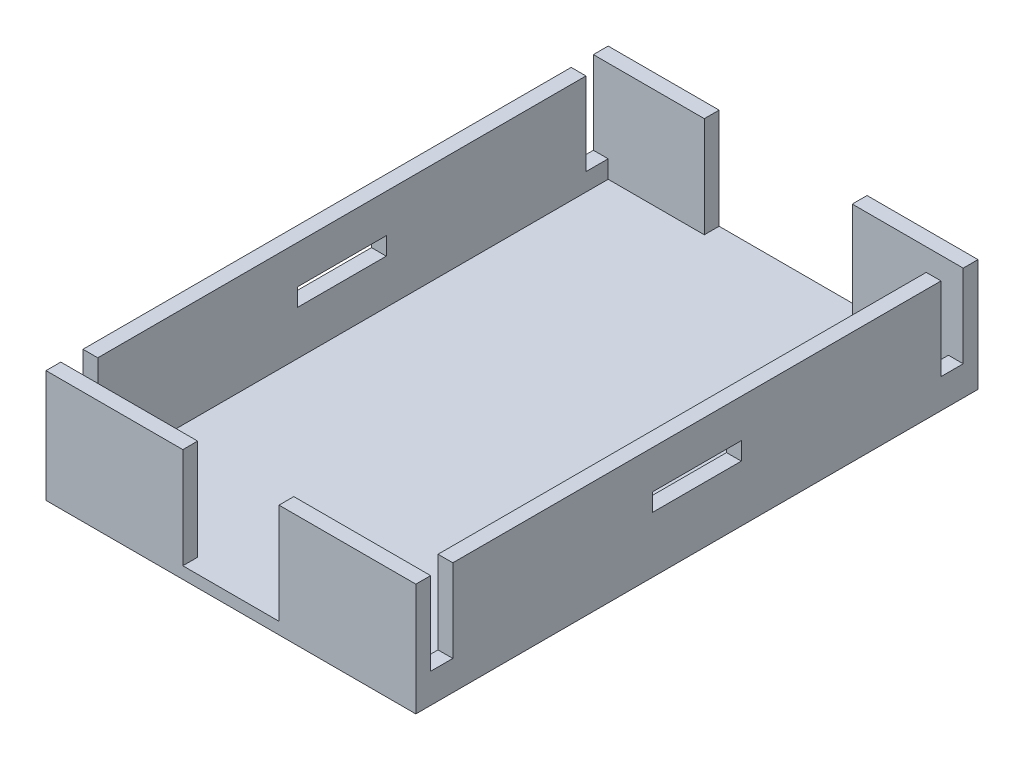
SolidWorks part; units mm, degrees
ref_plane "Front Plane" through (0, 0, 0) normal (0, 0, 1) x (1, 0, 0)
ref_plane "Top Plane" through (0, 0, 0) normal (0, 1, 0) x (1, 0, 0)
ref_plane "Right Plane" through (0, 0, 0) normal (1, 0, 0) x (0, 0, -1)
sketch "Sketch1" plane through (0, 0, 0) normal (0, 1, 0) x (1, 0, 0)
  line L1 (-12.5, -19) -> (12.5, -19)
  line L2 (-12.5, -19) -> (-12.5, 19)
  line L3 (-12.5, 19) -> (12.5, 19)
  line L4 (12.5, -19) -> (12.5, 19)
  line L5 (-12.5, -19) -> (12.5, 19) construction
  line L6 (-12.5, 19) -> (12.5, -19) construction
  point P0 (0, 0)
  dimension "D1" = 25
  dimension "D2" = 38
extrude "Boss-Extrude1" add sketch "Sketch1" along normal blind 7.6
sketch "Sketch2" plane through (0, 7.6, 0) normal (0, 1, 0) x (1, 0, 0)
  line L0 (-12.5, 19) -> (-12.5, -19) construction
  line L1 (-11.5, -18) -> (11.5, -18)
  line L2 (-11.5, -18) -> (-11.5, 18)
  line L3 (-11.5, 18) -> (11.5, 18)
  line L4 (11.5, -18) -> (11.5, 18)
  line L5 (-11.5, -18) -> (11.5, 18) construction
  line L6 (-11.5, 18) -> (11.5, -18) construction
  line L7 (-11.5, 18) -> (-12.5, 18)
  line L8 (-11.5, 18) -> (-11.5, 16.5)
  line L9 (-11.5, 16.5) -> (-12.5, 16.5)
  line L10 (-12.5, 18) -> (-12.5, 16.5)
  line L11 (0, -55) -> (0, 55) construction
  line L12 (11.5, 16.5) -> (12.5, 16.5)
  line L13 (12.5, 18) -> (12.5, 16.5)
  line L14 (11.5, 18) -> (12.5, 18)
  line L15 (-55, 0) -> (55, 0) construction
  line L16 (11.5, -16.5) -> (12.5, -16.5)
  line L17 (12.5, -18) -> (12.5, -16.5)
  line L18 (11.5, -18) -> (12.5, -18)
  line L19 (-11.5, -16.5) -> (-12.5, -16.5)
  line L20 (-12.5, -18) -> (-12.5, -16.5)
  line L21 (-11.5, -18) -> (-12.5, -18)
  point P0 (0, 0)
  line M5 (12.5, -19) -> (12.5, 19)
  line M7 (-12.5, 19) -> (-12.5, -19)
  dimension "D1" = 23
  dimension "D2" = 36
  dimension "D3" = 1.5
extrude "Cut-Extrude1" cut sketch "Sketch2" against normal blind 6.8 contours L1 L4 L3 L2 region at (0, 7.6, 0)
extrude "Cut-Extrude2" cut sketch "Sketch2<3>" against normal blind 5.6 contours L9 L2 L7 M7 | L14 L4 L12 M5 | L21 L2 L19 M7 | L4 L18 L16 M5 region at (-12, 7.6, 17.25) region at (12, 7.6, 17.25) region at (-12, 7.6, -17.25) region at (12, 7.6, -17.25)
sketch "Sketch2<3>" plane through (0, 7.6, 0) normal (0, 1, 0) x (1, 0, 0) same geometry as "Sketch2"
sketch "Sketch3" plane through (0, 0, 0) normal (1, 0, 0) x (0, 0, -1)
  line L0 (0, 0) -> (0, 7.6) construction
  line L1 (-16.5, 7.6) -> (16.5, 7.6) construction
  line L2 (-19, 0) -> (19, 0) construction
  line L3 (-3, 3.8) -> (3, 3.8)
  line L4 (-3, 3.8) -> (-3, 5)
  line L5 (-3, 5) -> (3, 5)
  line L6 (3, 3.8) -> (3, 5)
  line L7 (-3, 3.8) -> (3, 5) construction
  line L8 (-3, 5) -> (3, 3.8) construction
  point P5 (0, 4.4)
  dimension "D1" = 6
  dimension "D2" = 1.2
  dimension "D3" = 3.8
extrude "Cut-Extrude3" cut sketch "Sketch3" against normal through all both and the other way through all
sketch "Sketch4" plane through (0, 7.6, 0) normal (0, 1, 0) x (1, 0, 0)
  line L0 (0, -18) -> (0, -19) construction
  line L1 (-12.5, -18) -> (12.5, -18) construction
  line L2 (-12.5, -19) -> (12.5, -19) construction
  line L3 (0, 18) -> (0, 19) construction
  line L4 (-3.25, -19) -> (3.25, -19)
  line L5 (-3.25, -19) -> (-3.25, -18)
  line L6 (-3.25, -18) -> (3.25, -18)
  line L7 (3.25, -19) -> (3.25, -18)
  line L8 (-3.25, -19) -> (3.25, -18) construction
  line L9 (-3.25, -18) -> (3.25, -19) construction
  line L10 (-12.5, 18) -> (12.5, 18) construction
  line L11 (12.5, 19) -> (-12.5, 19) construction
  line L13 (-5, 18) -> (5, 18)
  line L14 (-5, 18) -> (-5, 19)
  line L15 (-5, 19) -> (5, 19)
  line L16 (5, 18) -> (5, 19)
  line L17 (-5, 18) -> (5, 19) construction
  line L18 (-5, 19) -> (5, 18) construction
  point P6 (0, -18.5)
  point P17 (0, 18.5)
  dimension "D1" = 6.5
  dimension "D2" = 10
extrude "Cut-Extrude4" cut sketch "Sketch4" against normal up to surface (6.8 mm away) up to face at (0, 0.8, 0)
